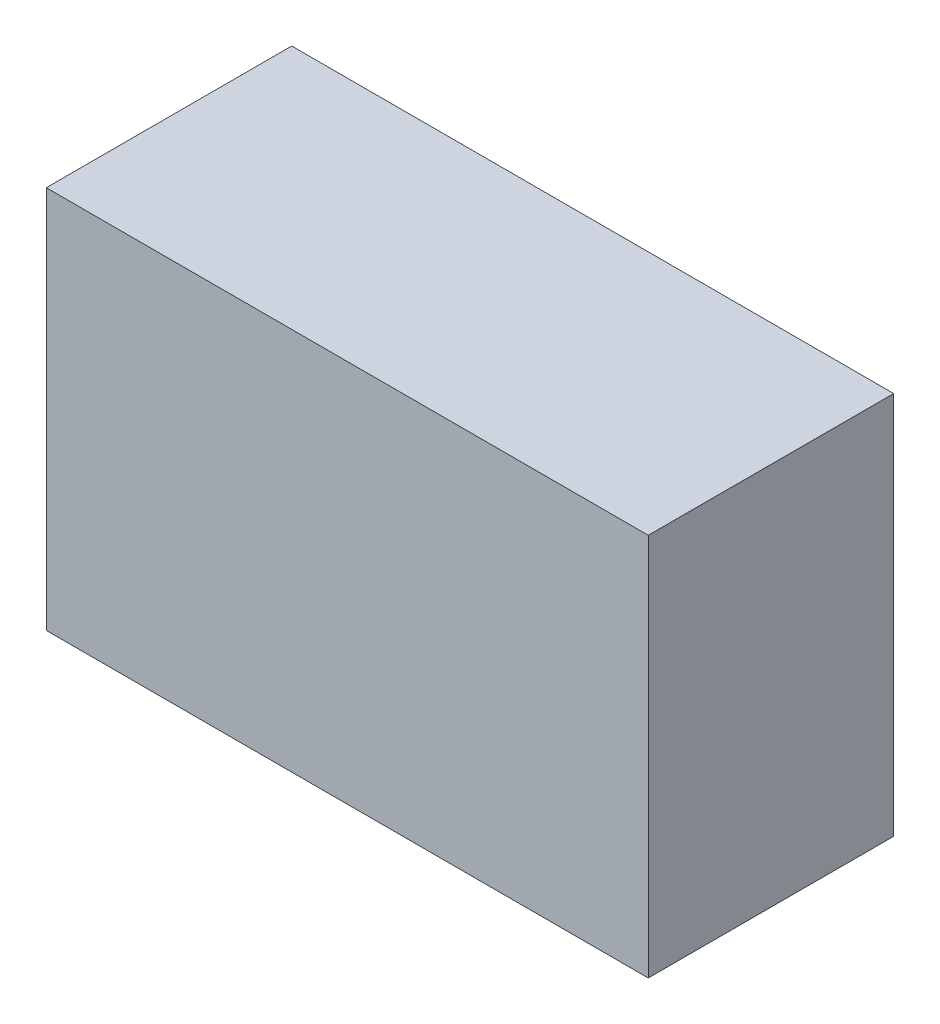
SolidWorks part; units mm, degrees
material "1060 Alloy"
ref_plane "Front" through (0, 0, 0) normal (0, 0, 1) x (1, 0, 0)
ref_plane "Top" through (0, 0, 0) normal (0, 1, 0) x (1, 0, 0)
ref_plane "Right" through (0, 0, 0) normal (1, 0, 0) x (0, 0, -1)
sketch "Sketch3" plane through (0, 0, 0) normal (0, 0, 1) x (1, 0, 0)
  line L0 (-0.127, -6.35) -> (30.1755, -6.35)
  line L1 (0, 0) -> (31.1484, 0)
  line L2 (0, 0) -> (0, -19.8376)
  line L3 (0, -19.8376) -> (31.1484, -19.8376)
  line L4 (31.1484, 0) -> (31.1484, -19.8376)
  line L5 (15.5742, -19.8376) -> (15.5742, 0) construction
  line L6 (15.5742, -6.35) -> (8.0621, -19.3614) construction
  line L15 (12.5496, -11.5887) -> (15.5742, -13.335) construction
  line L16 (15.5742, -6.35) -> (22.9274, -19.0862) construction
  circle A0 centre (15.5742, -6.35) radius 6.0492 construction
  point P14 (0, -6.35)
  point P17 (9.525, -6.35)
  point P19 (31.1484, -6.35)
  point P20 (7.7871, -19.8376)
  point P24 (23.3613, -19.8376)
  dimension "D2" = 6.35
  dimension "D6" = 3.4925
  dimension "D3" = 60
  dimension "D1" = 9.525
  dimension "D4" = 9.525
  dimension "D5" = 60
extrude "Boss-Extrude1" add sketch "Sketch3" along normal mid plane 12.7
sketch "Sketch4" plane through (0, 0, 0) normal (-1, 0, 0) x (0, 0, 1)
  circle A0 centre (0, -6.35) radius 3.175
  dimension "D1" = 6.35
extrude "Cut-Extrude1" cut sketch "Sketch4" against normal blind 9.525
ref_plane "Plane1" through (7.7871, -19.8376, 0) normal (-0.5, -0.866, 0) x (-0.866, 0.5, 0)
ref_plane "Mirror Plane" through (15.5742, 0, 0) normal (-1, 0, 0) x (0, 0, 1)
sketch "Sketch5" plane through (7.7871, -19.8376, 0) normal (-0.5, -0.866, 0) x (-0.866, 0.5, 0)
  circle A0 centre (0, 0) radius 3.175
  dimension "D1" = 6.35
extrude "Cut-Extrude5" cut sketch "Sketch5" against normal blind 9.525 and the other way up to next
sketch "Sketch6" plane through (0, 0, -6.35) normal (0, 0, -1) x (-1, 0, 0)
  circle A0 centre (-15.5742, -6.35) radius 3.175
  dimension "D1" = 6.35
extrude "Cut-Extrude6" cut sketch "Sketch6" against normal blind 9.525
mirror "Mirror1" about plane through (15.5742, 0, 0) normal (-1, 0, 0) of "Cut-Extrude5"
equation "\"truss_member_od\" = .25in"
equation "\"truss_member_id\"= 0in"
equation "\"truss_member_L1\" = 2.125in"
equation "\"connector_hole_depth\" = .375in"
equation "\"D1@Boss-Extrude1\"=\"truss_member_od\"*2"
equation "\"D6@Sketch3\"=\"truss_member_od\"/2*1.1"
equation "\"D1@Sketch4\"=\"truss_member_od\""
equation "\"D1@Cut-Extrude1\"=\"connector_hole_depth\""
equation "\"D1@Sketch3\"=\"connector_hole_depth\""
equation "\"D4@Sketch3\"=\"connector_hole_depth\""
equation "\"D1@Sketch5\"=\"truss_member_od\""
equation "\"D1@Cut-Extrude5\"=\"connector_hole_depth\""
equation "\"D1@Cut-Extrude6\"=\"connector_hole_depth\""
equation "\"D1@Sketch6\"=\"truss_member_od\""
